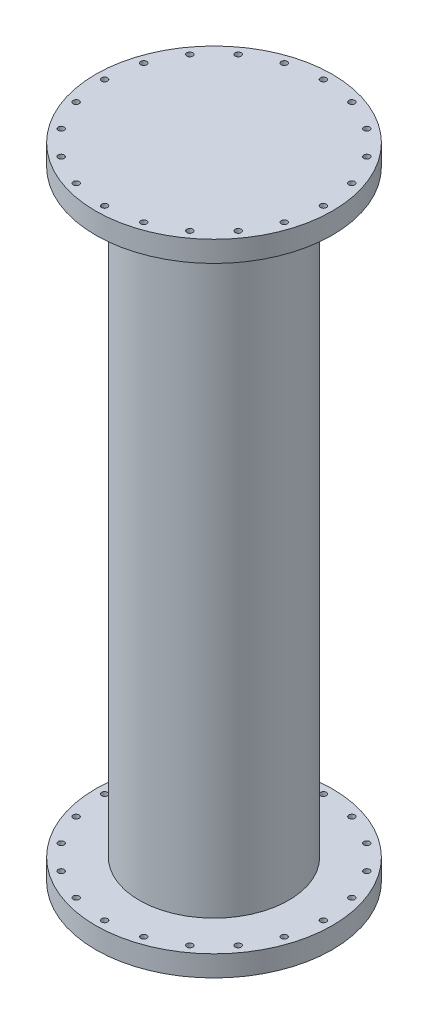
SolidWorks part; units mm, degrees
ref_plane "Plan de face" through (0, 0, 0) normal (0, 0, 1) x (1, 0, 0)
ref_plane "Plan de dessus" through (0, 0, 0) normal (0, 1, 0) x (1, 0, 0)
ref_plane "Plan de droite" through (0, 0, 0) normal (1, 0, 0) x (0, 0, -1)
sketch "Esquisse1" plane through (0, 0, 0) normal (0, 0, 1) x (1, 0, 0)
  line L0 (0, 0) -> (0, -1756.5308) construction
  line L1 (0, 0) -> (396, 0)
  line L2 (0, 0) -> (0, -70)
  line L3 (0, -70) -> (200, -70)
  line L4 (396, 0) -> (396, -70)
  line L26 (250, -70) -> (396, -70)
  line L27 (250, -2070) -> (396, -2070)
  line L29 (200, -70) -> (200, -2070)
  line L31 (250, -70) -> (250, -2070)
  line L32 (0, -2070) -> (200, -2070)
  line L33 (0, -2070) -> (0, -2140)
  line L34 (0, -2140) -> (396, -2140)
  line L35 (396, -2070) -> (396, -2140)
  dimension "D1" = 396
  dimension "D2" = 70
  dimension "D3" = 70
  dimension "D4" = 396
  dimension "D5" = 250
  dimension "D6" = 200
  dimension "D7" = 2000
revolve "Révolution1" add sketch "Esquisse1" angle 360 about L0
sketch "Esquisse2" plane through (0, 0, 0) normal (0, 1, 0) x (1, 0, 0)
  circle A0 centre (366, 0) radius 10
  dimension "D2" = 20
  dimension "D1" = 366
extrude "Enlèv. mat.-Extru.1" cut sketch "Esquisse2" against normal through all
pattern_circular "Répétition circulaire1" count 20 over 360 about axis through (0, 0, 0) along (0, 1, 0) of "Enlèv. mat.-Extru.1"
sketch "Esquisse3" plane through (0, -2340, 0) normal (0, 1, 0) x (1, 0, 0)
  circle A0 centre (0, 0) radius 255.3935
